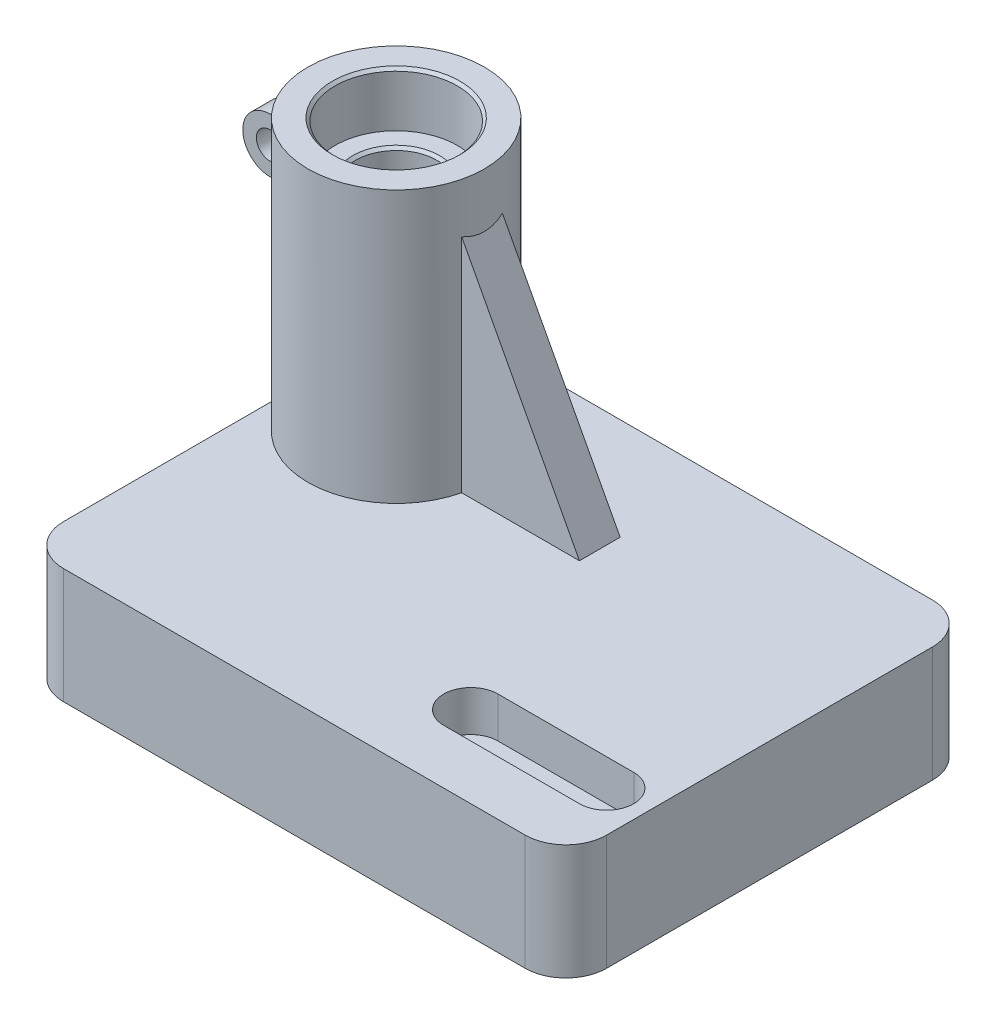
SolidWorks part; units mm, degrees
ref_plane "Front Plane" through (0, 0, 0) normal (0, 0, 1) x (1, 0, 0)
ref_plane "Top Plane" through (0, 0, 0) normal (0, 1, 0) x (1, 0, 0)
ref_plane "Right Plane" through (0, 0, 0) normal (1, 0, 0) x (0, 0, -1)
sketch "Sketch1" plane through (0, 0, 0) normal (0, 1, 0) x (1, 0, 0)
  line L1 (-200, 150) -> (200, 150)
  line L2 (-200, 150) -> (-200, -150)
  line L3 (-200, -150) -> (200, -150)
  line L4 (200, 150) -> (200, -150)
  line L5 (-200, 150) -> (200, -150) construction
  line L6 (-200, -150) -> (200, 150) construction
  point P0 (0, 0)
  dimension "D1" = 400
  dimension "D2" = 300
extrude "Boss-Extrude1" add sketch "Sketch1" along normal blind 85
sketch "Sketch2" plane through (0, 85, 0) normal (0, 1, 0) x (1, 0, 0)
  line L0 (200, 150) -> (-200, 150) construction
  line L1 (-200, 150) -> (-200, -150) construction
  circle A0 centre (-135, 60) radius 65
  dimension "D1" = 130
  dimension "D2" = 90
  dimension "D3" = 65
extrude "Boss-Extrude2" add sketch "Sketch2" along normal blind 200
fillet "Fillet1" radius 30 4 edges at (-200, 42.5, -150) (200, 42.5, -150) (200, 42.5, 150) (-200, 42.5, 150)
sketch "Sketch3" plane through (0, 85, 0) normal (0, 1, 0) x (1, 0, 0)
  line L0 (70, -70) -> (170, -70)
  line L1 (170, -110) -> (70, -110)
  line L2 (200, -120) -> (200, 120) construction
  line L3 (-170, -150) -> (170, -150) construction
  arc A0 (70, -70) -> (70, -110) centre (70, -90) ccw
  arc A1 (170, -110) -> (170, -70) centre (170, -90) ccw
  dimension "D1" = 40
  dimension "D3" = 30
  dimension "D4" = 60
  dimension "D2" = 100
extrude "Cut-Extrude1" cut sketch "Sketch3" against normal blind 30
ref_plane "Plane1" through (0, 0, -60) normal (0, 0, 1) x (1, 0, 0)
sketch "Sketch4" plane through (0, 0, -60) normal (0, 0, 1) x (1, 0, 0)
  line L0 (15, 85) -> (-70, 245)
  line L1 (-170, 85) -> (170, 85) construction
  line L3 (-70, 85) -> (-70, 285) construction
  dimension "D1" = 160
  dimension "D2" = 85
rib "Rib1" sketch "Sketch4" sketch "Sketch4" thickness 30 extrusion direction parallel to sketch draft on no parameters "D1"=30
sketch "Sketch5" plane through (0, 0, -60) normal (0, 0, 1) x (1, 0, 0)
  line L0 (-200, 285) -> (-200, 85) construction
  line L1 (-220, 249) -> (-200, 249)
  line L2 (-220, 209) -> (-200, 209)
  line L3 (-200, 249) -> (-200, 209)
  line L4 (-70, 285) -> (-200, 285) construction
  arc A0 (-220, 249) -> (-220, 209) centre (-220, 229) ccw
  circle A1 centre (-220, 229) radius 10
  dimension "D1" = 40
  dimension "D4" = 20
  dimension "D2" = 20
  dimension "D3" = 36
sketch "Sketch6" plane through (0, 285, 0) normal (0, 1, 0) x (1, 0, 0)
  circle A0 centre (-135, 60) radius 30
  dimension "D1" = 60
extrude "Cut-Extrude2" cut sketch "Sketch6" against normal through all
sketch "Sketch7" plane through (0, 0, 0) normal (0, 1, 0) x (1, 0, 0)
  circle A0 centre (-135, 60) radius 45
  dimension "D1" = 90
extrude "Cut-Extrude3" cut sketch "Sketch7" along normal blind 40
sketch "Sketch8" plane through (0, 285, 0) normal (0, 1, 0) x (1, 0, 0)
  circle A0 centre (-135, 60) radius 45
  dimension "D1" = 90
extrude "Cut-Extrude4" cut sketch "Sketch8" against normal blind 40
chamfer "Chamfer1" distance 2 angle 45 4 edges at (-135, 0, -15) (-135, 40, -30) (-135, 245, -30) (-135, 285, -15)
ref_plane "Plane2" through (-240, 0, 0) normal (-1, 0, 0) x (0, 0, 1)
sketch "Sketch9" plane through (-240, 0, 0) normal (-1, 0, 0) x (0, 0, 1)
  line L0 (-60, 285) -> (-60, 166.323) construction
  line L1 (5, 285) -> (-125, 285) construction
  line L2 (-13, 285) -> (-107, 285) construction
  line L3 (-68, 249) -> (-52, 249)
  line L4 (-68, 249) -> (-68, 209)
  line L5 (-68, 209) -> (-52, 209)
  line L6 (-52, 249) -> (-52, 209)
  line L7 (-68, 249) -> (-52, 209) construction
  line L8 (-68, 209) -> (-52, 249) construction
  point P4 (-60, 229)
  dimension "D1" = 36
  dimension "D2" = 16
  dimension "D3" = 40
extrude "Boss-Extrude3" add sketch "Sketch9" against normal up to next
fillet "Fillet2" radius 20 2 edges at (-240, 209, -60) (-240, 249, -60)
sketch "Sketch10" plane through (0, 0, -52) normal (0, 0, 1) x (1, 0, 0)
  circle A0 centre (-220, 229) radius 10
  dimension "D1" = 20
extrude "Cut-Extrude5" cut sketch "Sketch10" against normal through all and the other way through all
